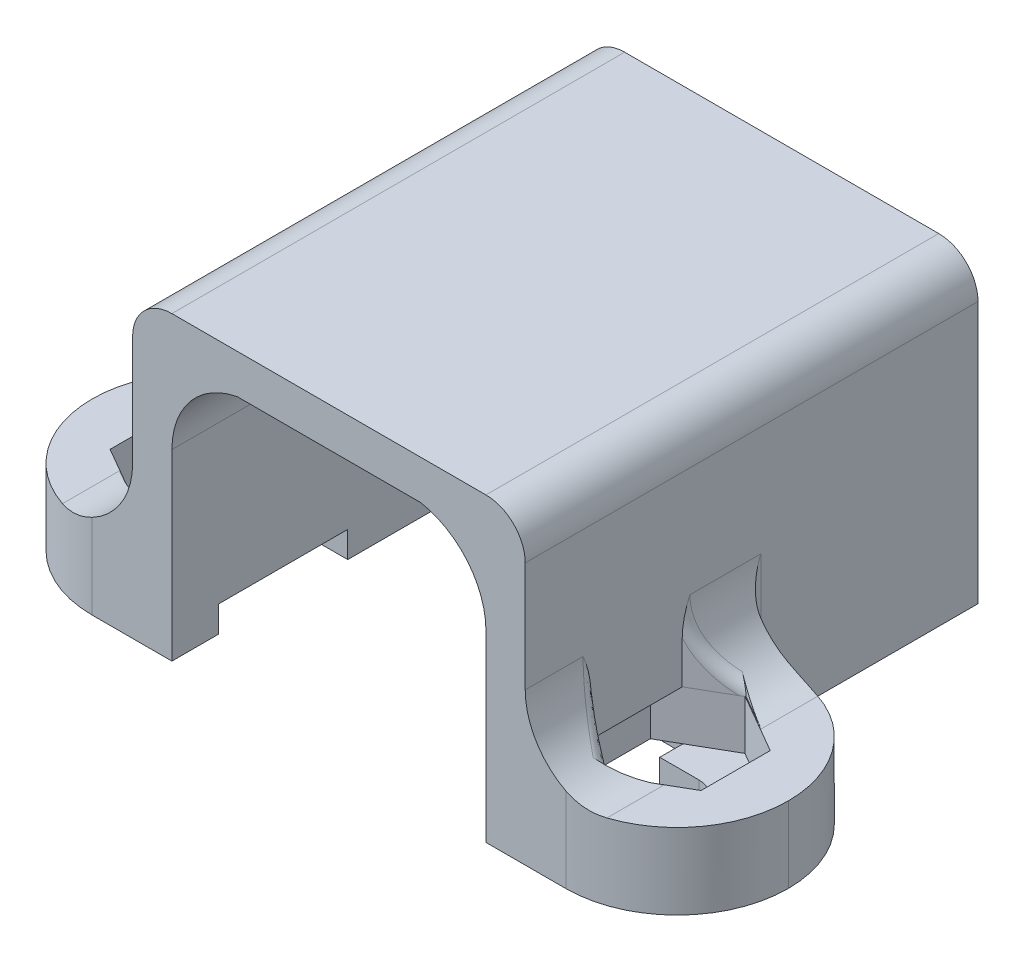
SolidWorks part; units mm, degrees
material "ABS"
ref_plane "Front Plane" through (0, 0, 0) normal (0, 0, 1) x (1, 0, 0)
ref_plane "Top Plane" through (0, 0, 0) normal (0, 1, 0) x (1, 0, 0)
ref_plane "Right Plane" through (0, 0, 0) normal (1, 0, 0) x (0, 0, -1)
sketch "Sketch1" plane through (0, 0, 0) normal (0, 0, 1) x (1, 0, 0)
  line L0 (0, 0) -> (0, 10)
  line L1 (1.5, 11.5) -> (13.5, 11.5)
  line L2 (15, 10) -> (15, 0)
  line L3 (13.5, 0) -> (13.5, 7)
  line L4 (4, 10) -> (11, 10)
  line L5 (13.5, 0) -> (15, 0)
  line L6 (0, 0) -> (1.5, 0)
  line L7 (1.5, 0) -> (1.5, 7)
  arc A0 (0, 10) -> (1.5, 11.5) centre (1.5, 10) cw
  arc A1 (13.5, 11.5) -> (15, 10) centre (13.5, 10) cw
  arc A2 (1.5, 7) -> (4, 10) centre (4.55, 7) cw
  arc A3 (13.5, 7) -> (11, 10) centre (10.45, 7) ccw
  dimension "D1" = 1.5
  dimension "D2" = 15
  dimension "D3" = 11.5
  dimension "D4" = 1.5
  dimension "D5" = 11.5
  dimension "D6" = 1.5
  dimension "D7" = 7
  dimension "D8" = 7
extrude "Boss-Extrude1" add sketch "Sketch1" against normal blind 17.3
sketch "Sketch2" plane through (0, 0, 0) normal (0, 0, 1) x (1, 0, 0)
  line L0 (0, 0) -> (-5.8, 0)
  line L1 (-5.8, 0) -> (-5.8, 2.9)
  line L2 (-5.8, 2.9) -> (-2.9, 2.9)
  line L3 (0, 5.8) -> (0, 0)
  line L4 (0, 10) -> (0, 0) construction
  line L5 (7.5, -988.5) -> (7.5, 49011.5) construction
  line L6 (13.5, 11.5) -> (1.5, 11.5) construction
  line L7 (15, 5.8) -> (15, 0)
  line L8 (20.8, 0) -> (20.8, 2.9)
  line L9 (15, 0) -> (20.8, 0)
  line L10 (20.8, 2.9) -> (17.9, 2.9)
  arc A0 (-2.9, 2.9) -> (0, 5.8) centre (-2.9, 5.8) ccw
  arc A1 (17.9, 2.9) -> (15, 5.8) centre (17.9, 5.8) cw
  point P14 (7.5, 11.5)
  dimension "D1" = 5.8
  dimension "D2" = 2.9
  dimension "D3" = 2.9
extrude "Boss-Extrude2" add sketch "Sketch2" against normal blind 8.5
fillet "Fillet1" radius 4.25 4 edges at (20.8, 1.45, -8.5) (20.8, 1.45, 0) (-5.8, 1.45, 0) (-5.8, 1.45, -8.5)
fillet "Fillet2" radius 0.5 2 edges at (15, 2.9, -8.5) (0, 2.9, -8.5)
hole_wizard "#2-56 Tapped Hole1" positions "Sketch4" profile "Sketch3" tap size "#2-56" standard "Ansi Inch"
sketch "Sketch4" plane through (0, 0, 0) normal (0, -1, 0) x (1, 0, 0)
  line L1 (-1.55, 0) -> (1.5, 0) construction
  line L2 (1.5, -17.3) -> (1.5, 0) construction
  line L3 (13.5, -17.3) -> (13.5, 0) construction
  point P0 (-1.5, -4.25)
  point P1 (16.5, -4.25)
  dimension "D1" = 4.25
  dimension "D2" = 3
  dimension "D3" = 3
sketch "Sketch3" plane through (-1.5, 0, -4.25) normal (1, 0, 0) x (0, 0, -1)
  line L0 (0, 0) -> (0, 6.2642)
  line L1 (0, 6.2642) -> (0.889, 5.73)
  line L2 (0.889, 5.73) -> (0.889, 0)
  line L5 (0.889, 0) -> (0, 0)
  line L10 (0, 6.2642) -> (-0.889, 5.73) construction
  line L11 (0, -6.35) -> (0, 107.95) construction
  dimension "Tap Drill Dia." = 1.778
  dimension "Tap Drill Depth" = 5.73
  dimension "Drill Angle" = 118
cosmetic thread "Hole Thread1" parameters "D1"=4.0194, "D2"=2.1844
cosmetic thread "Hole Thread2" parameters "D1"=4.0194, "D2"=2.1844
sketch "Sketch6" plane through (0, 0, 0) normal (0, -1, 0) x (1, 0, 0)
  line L0 (7.5, -1000) -> (7.5, 49000) construction
  line L1 (0.79, -2.9279) -> (-1.5, -1.6057)
  line L2 (-1.5, -1.6057) -> (-3.79, -2.9279)
  line L3 (-3.79, -2.9279) -> (-3.79, -5.5721)
  line L4 (-3.79, -5.5721) -> (-1.5, -6.8943)
  line L5 (-1.5, -6.8943) -> (0.79, -5.5721)
  line L6 (0.79, -5.5721) -> (0.79, -2.9279)
  line L7 (4, 0) -> (11, 0) construction
  line L8 (16.5, -6.8943) -> (14.21, -5.5721)
  line L9 (14.21, -5.5721) -> (14.21, -2.9279)
  line L10 (14.21, -2.9279) -> (16.5, -1.6057)
  line L11 (16.5, -1.6057) -> (18.79, -2.9279)
  line L12 (18.79, -2.9279) -> (18.79, -5.5721)
  line L13 (18.79, -5.5721) -> (16.5, -6.8943)
  circle A0 centre (-1.5, -4.25) radius 2.29 construction
  point P15 (7.5, 0)
  dimension "D1" = 2.29
  dimension "D2" = 2.29
extrude "Cut-Extrude3" cut sketch "Sketch6" along normal blind 1.9 from offset 2.9 offset against normal yes
sketch "Sketch7" plane through (0, 11.5, 0) normal (0, 1, 0) x (1, 0, 0)
  line L0 (0, 5.9994) -> (0, 2.5006)
  line L1 (-3.84, 2.9279) -> (-1.55, 1.6057)
  line L2 (-1.55, 1.6057) -> (0, 2.5006)
  line L3 (7.5, -982.7) -> (7.5, 49017.3) construction
  line L4 (0, 5.9994) -> (-1.55, 6.8943)
  line L5 (-1.55, 6.8943) -> (-3.84, 5.5721)
  line L6 (-3.84, 5.5721) -> (-3.84, 2.9279)
  line L8 (13.5, 17.3) -> (1.5, 17.3) construction
  line L9 (0.74, 2.9279) -> (0.74, 4.25) [skipped]
  line L10 (15, 5.9994) -> (16.55, 6.8943)
  line L11 (15, 5.9994) -> (15, 2.5006)
  line L12 (16.55, 1.6057) -> (15, 2.5006)
  line L13 (18.84, 2.9279) -> (16.55, 1.6057)
  line L14 (18.84, 5.5721) -> (18.84, 2.9279)
  line L15 (16.55, 6.8943) -> (18.84, 5.5721)
  circle A0 centre (-1.55, 4.25) radius 2.29 construction
  point P14 (7.5, 17.3)
  dimension "D1" = 2.6443
  dimension "D2" = 2.29
  dimension "D3" = 3.4987
extrude "Cut-Extrude2" cut sketch "Sketch7" against normal blind 8.6
sketch "Sketch8" plane through (0, 0, 0) normal (0, -1, 0) x (1, 0, 0)
  line L0 (1.5, -1.781) -> (0, -1.781)
  line L1 (1.5, -17.3) -> (1.5, 0) construction
  line L2 (0, -1.781) -> (0, -3.361)
  line L3 (0, -3.361) -> (-1.5, -3.361)
  line L4 (-1.5, -3.361) -> (-1.5, -5.139)
  line L5 (-1.5, -5.139) -> (0, -5.139)
  line L6 (0, -5.139) -> (0, -6.719)
  line L7 (0, -6.719) -> (1.5, -6.719)
  line L8 (7.5, -1000) -> (7.5, 49000) construction
  line L9 (4, 0) -> (11, 0) construction
  line L10 (13.5, -1.781) -> (15, -1.781)
  line L11 (15, -1.781) -> (15, -3.361)
  line L12 (15, -3.361) -> (16.5, -3.361)
  line L13 (16.5, -3.361) -> (16.5, -5.139)
  line L14 (16.5, -5.139) -> (15, -5.139)
  line L15 (15, -5.139) -> (15, -6.719)
  line L16 (15, -6.719) -> (13.5, -6.719)
  line L17 (1.5, -1.781) -> (1.5, -6.719)
  line L18 (13.5, -1.781) -> (13.5, -6.719)
  circle A0 centre (-1.5, -4.25) radius 0.889 construction
  point P20 (7.5, 0)
  dimension "D1" = 1.58
  dimension "D2" = 1.58
extrude "Cut-Extrude5" cut sketch "Sketch8" against normal blind 1
fillet "Fillet4" radius 0.5 4 edges at (15.4176, 4.3008, -6.2405) (15.4176, 4.3008, -2.2595) (-0.4176, 4.3008, -2.2595) (-0.4176, 4.3008, -6.2405)
